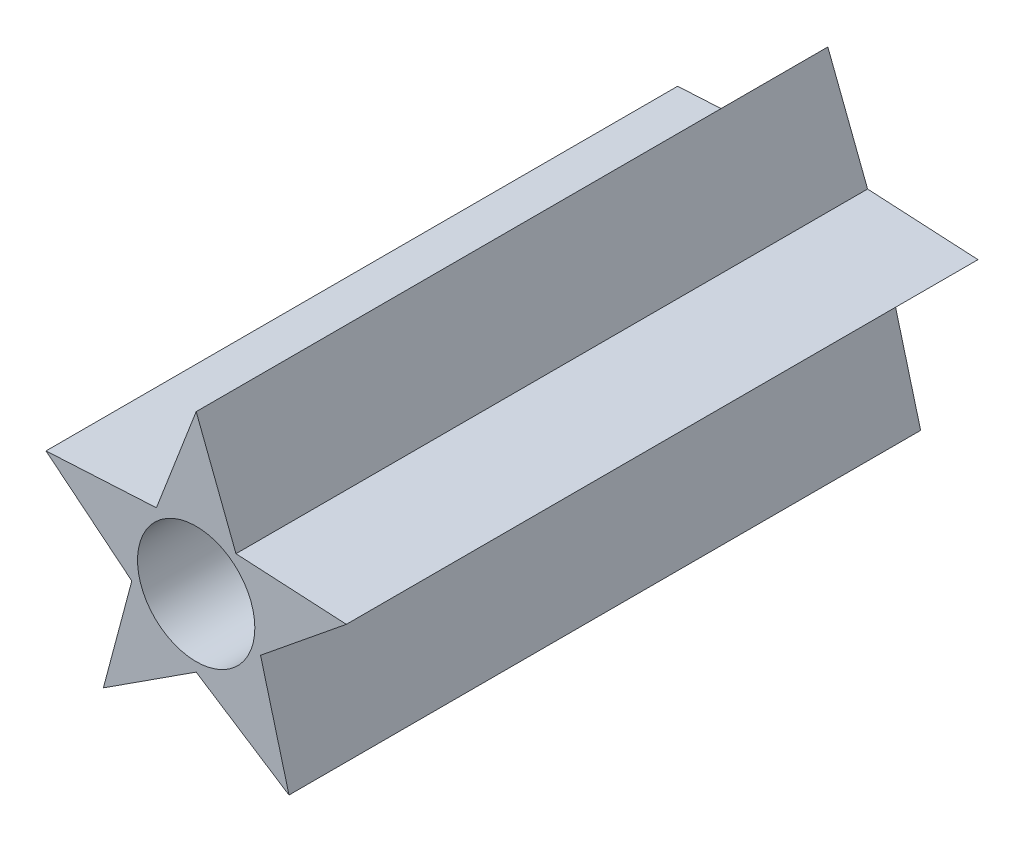
SolidWorks part; units mm, degrees
ref_plane "Front Plane" through (0, 0, 0) normal (0, 0, 1) x (1, 0, 0)
ref_plane "Top Plane" through (0, 0, 0) normal (0, 1, 0) x (1, 0, 0)
ref_plane "Right Plane" through (0, 0, 0) normal (1, 0, 0) x (0, 0, -1)
sketch "Sketch1" plane through (0, 0, 0) normal (0, 0, 1) x (1, 0, 0)
  line L0 (0, 17.5) -> (-4.4084, 6.0676)
  line L1 (10.2862, -14.1578) -> (16.6435, 5.4078) construction
  line L2 (16.6435, 5.4078) -> (0, 17.5) construction
  line L3 (0, 17.5) -> (-16.6435, 5.4078) construction
  line L4 (-16.6435, 5.4078) -> (-10.2862, -14.1578) construction
  line L5 (-10.2862, -14.1578) -> (10.2862, -14.1578) construction
  line L6 (7.1329, -2.3176) -> (4.4084, 6.0676) construction
  line L7 (4.4084, 6.0676) -> (-4.4084, 6.0676) construction
  line L8 (-4.4084, 6.0676) -> (-7.1329, -2.3176) construction
  line L9 (-7.1329, -2.3176) -> (0, -7.5) construction
  line L10 (0, -7.5) -> (7.1329, -2.3176) construction
  line L11 (-4.4084, 6.0676) -> (-16.6435, 5.4078)
  line L12 (-16.6435, 5.4078) -> (-7.1329, -2.3176)
  line L13 (-7.1329, -2.3176) -> (-10.2862, -14.1578)
  line L14 (-10.2862, -14.1578) -> (0, -7.5)
  line L15 (0, -7.5) -> (10.2862, -14.1578)
  line L16 (10.2862, -14.1578) -> (7.1329, -2.3176)
  line L17 (7.1329, -2.3176) -> (16.6435, 5.4078)
  line L18 (16.6435, 5.4078) -> (4.4084, 6.0676)
  line L19 (4.4084, 6.0676) -> (0, 17.5)
  circle A0 centre (0, 0) radius 17.5 construction
  circle A1 centre (0, 0) radius 7.5 construction
  dimension "D1" = 35
  dimension "D2" = 15
extrude "Boss-Extrude1" add sketch "Sketch1" along normal blind 70
sketch "Sketch2" plane through (0, 0, 70) normal (0, 0, 1) x (1, 0, 0)
  line L0 (16.6435, 5.4078) -> (4.4084, 6.0676) construction
  line L1 (16.6435, 5.4078) -> (4.4084, 6.0676)
  line L2 (4.4084, 6.0676) -> (3.8206, 5.2586)
  circle A0 centre (0, 0) radius 6.5
  dimension "D1" = 1
extrude "Cut-Extrude1" cut sketch "Sketch2" against normal through all contours A0 region at (0, 0, 70)
